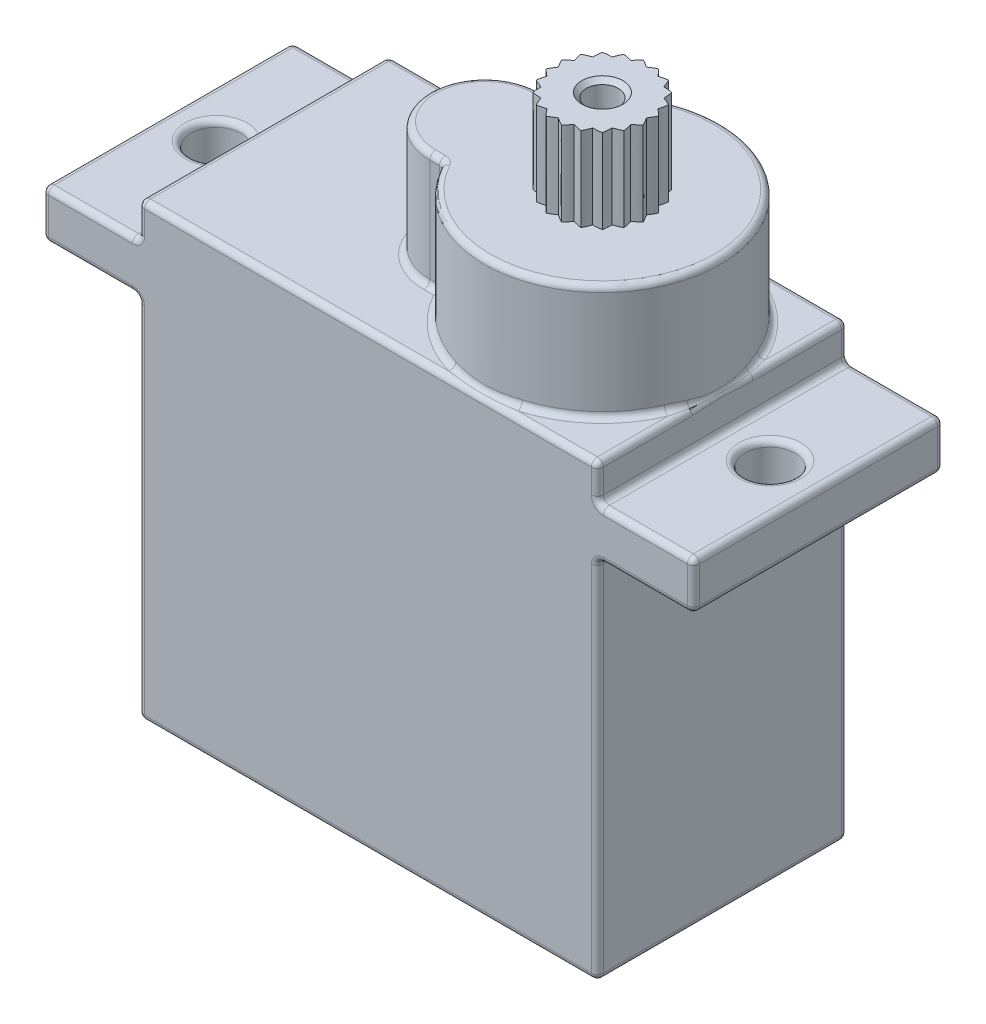
SolidWorks part; units mm, degrees
other "Camera1"
ref_plane "Front" through (0, 0, 0) normal (0, 0, 1) x (1, 0, 0)
ref_plane "Top" through (0, 0, 0) normal (0, 1, 0) x (1, 0, 0)
ref_plane "Right" through (0, 0, 0) normal (1, 0, 0) x (0, 0, -1)
sketch "Sketch1" plane through (0, 0, 0) normal (0, 1, 0) x (1, 0, 0)
  line L1 (11.47, -6.25) -> (-11.47, -6.25)
  line L2 (11.47, -6.25) -> (11.47, 6.25)
  line L3 (11.47, 6.25) -> (-11.47, 6.25)
  line L4 (-11.47, -6.25) -> (-11.47, 6.25)
  line L5 (11.47, -6.25) -> (-11.47, 6.25) construction
  line L6 (11.47, 6.25) -> (-11.47, -6.25) construction
  point P0 (0, 0)
  dimension "D1" = 22.94
  dimension "D2" = 12.5
extrude "Boss-Extrude1" add sketch "Sketch1" along normal blind 22.5
ref_plane "Plane1" through (0, 18.3, 0) normal (0, -1, 0) x (-1, 0, 0)
sketch "Sketch2" plane through (0, 18.3, 0) normal (0, -1, 0) x (-1, 0, 0)
  line L0 (11.47, -6.25) -> (-11.47, -6.25) construction
  line L1 (-11.47, 6.25) -> (-16.27, 6.25)
  line L2 (-11.47, 6.25) -> (-11.47, -6.25)
  line L3 (-11.47, -6.25) -> (-16.27, -6.25)
  line L4 (-16.27, 6.25) -> (-16.27, -6.25)
  line L5 (0, 0) -> (0, -2.4329) construction
  line L6 (11.47, -6.25) -> (16.27, -6.25)
  line L7 (16.27, 6.25) -> (16.27, -6.25)
  line L8 (11.47, 6.25) -> (16.27, 6.25)
  line L9 (11.47, 6.25) -> (11.47, -6.25)
  circle A0 centre (-13.85, 0) radius 1.25
  circle A1 centre (13.85, 0) radius 1.25
  dimension "D2" = 2.5
  dimension "D1" = 4.8
  dimension "D3" = 13.85
extrude "Boss-Extrude2" add sketch "Sketch2" against normal blind 2.4
sketch "Sketch3" plane through (0, 22.5, 0) normal (0, 1, 0) x (1, 0, 0)
  line L0 (11.47, -6.25) -> (11.47, 6.25) construction
  line L1 (11.47, -6.25) -> (11.47, 6.25) construction
  line L2 (-0.41, 2.75) -> (0.2501, 2.75) construction
  line L3 (-0.41, -2.75) -> (0.2501, -2.75) construction
  line L4 (-0.41, 2.75) -> (0.2501, 2.75)
  line L5 (-0.41, -2.75) -> (0.2501, -2.75)
  line L6 (-0.41, 0) -> (5.47, 0) construction
  circle A0 centre (5.47, 0) radius 5.9 construction
  circle A1 centre (-0.41, 0) radius 2.75 construction
  arc A2 (-0.41, -2.75) -> (-0.41, 2.75) centre (-0.41, 0) cw
  arc A3 (0.2501, 2.75) -> (0.2501, -2.75) centre (5.47, 0) cw
  point P4 (11.37, 0)
  point P5 (-3.16, 0)
  dimension "D1" = 6
  dimension "D2" = 11.8
  dimension "D4" = 14.53
  dimension "D5" = 5.5
  dimension "D3" = 0.1
extrude "Boss-Extrude3" add sketch "Sketch3" along normal blind 5.75
sketch "Sketch4" plane through (0, 28.25, 0) normal (0, 1, 0) x (1, 0, 0)
  line L0 (5.47, 0) -> (5.47, 2.2) construction
  line L1 (5.47, 0) -> (6.1498, 2.0923) construction
  line L2 (5.47, 0) -> (5.8142, 2.1729) construction
  line L3 (5.47, 2.2) -> (5.7959, 2.4184) construction
  line L4 (5.7959, 2.4184) -> (5.8533, 2.4198) construction
  line L5 (6.1498, 2.0923) -> (5.9074, 2.4007) construction
  line L6 (5.9074, 2.4007) -> (5.8533, 2.4198) construction
  line L7 (6.1498, 2.0923) -> (6.5272, 2.1993) construction
  line L8 (6.5272, 2.1993) -> (6.5823, 2.183) construction
  line L9 (6.7631, 1.7798) -> (6.6278, 2.148) construction
  line L10 (6.6278, 2.148) -> (6.5823, 2.183) construction
  line L11 (6.7631, 1.7798) -> (7.1551, 1.7649) construction
  line L12 (7.1551, 1.7649) -> (7.2024, 1.7324) construction
  line L13 (7.2498, 1.2931) -> (7.2349, 1.6851) construction
  line L14 (7.2349, 1.6851) -> (7.2024, 1.7324) construction
  line L15 (7.2498, 1.2931) -> (7.618, 1.1578) construction
  line L16 (7.618, 1.1578) -> (7.653, 1.1123) construction
  line L17 (7.5623, 0.6798) -> (7.6693, 1.0572) construction
  line L18 (7.6693, 1.0572) -> (7.653, 1.1123) construction
  line L19 (7.5623, 0.6798) -> (7.8707, 0.4374) construction
  line L20 (7.8707, 0.4374) -> (7.8898, 0.3833) construction
  line L21 (7.67, 0) -> (7.8884, 0.3259) construction
  line L22 (7.8884, 0.3259) -> (7.8898, 0.3833) construction
  line L23 (7.67, 0) -> (7.8884, -0.3259) construction
  line L24 (7.8884, -0.3259) -> (7.8898, -0.3833) construction
  line L25 (7.5623, -0.6798) -> (7.8707, -0.4374) construction
  line L26 (7.8707, -0.4374) -> (7.8898, -0.3833) construction
  line L27 (7.5623, -0.6798) -> (7.6693, -1.0572) construction
  line L28 (7.6693, -1.0572) -> (7.653, -1.1123) construction
  line L29 (7.2498, -1.2931) -> (7.618, -1.1578) construction
  line L30 (7.618, -1.1578) -> (7.653, -1.1123) construction
  line L31 (7.2498, -1.2931) -> (7.2349, -1.6851) construction
  line L32 (7.2349, -1.6851) -> (7.2024, -1.7324) construction
  line L33 (6.7631, -1.7798) -> (7.1551, -1.7649) construction
  line L34 (7.1551, -1.7649) -> (7.2024, -1.7324) construction
  line L35 (6.7631, -1.7798) -> (6.6278, -2.148) construction
  line L36 (6.6278, -2.148) -> (6.5823, -2.183) construction
  line L37 (6.1498, -2.0923) -> (6.5272, -2.1993) construction
  line L38 (6.5272, -2.1993) -> (6.5823, -2.183) construction
  line L39 (6.1498, -2.0923) -> (5.9074, -2.4007) construction
  line L40 (5.9074, -2.4007) -> (5.8533, -2.4198) construction
  line L41 (5.47, -2.2) -> (5.7959, -2.4184) construction
  line L42 (5.7959, -2.4184) -> (5.8533, -2.4198) construction
  line L43 (5.47, -2.2) -> (5.1441, -2.4184) construction
  line L44 (5.1441, -2.4184) -> (5.0867, -2.4198) construction
  line L45 (4.7902, -2.0923) -> (5.0326, -2.4007) construction
  line L46 (5.0326, -2.4007) -> (5.0867, -2.4198) construction
  line L47 (4.7902, -2.0923) -> (4.4128, -2.1993) construction
  line L48 (4.4128, -2.1993) -> (4.3577, -2.183) construction
  line L49 (4.1769, -1.7798) -> (4.3122, -2.148) construction
  line L50 (4.3122, -2.148) -> (4.3577, -2.183) construction
  line L51 (4.1769, -1.7798) -> (3.7849, -1.7649) construction
  line L52 (3.7849, -1.7649) -> (3.7376, -1.7324) construction
  line L53 (3.6902, -1.2931) -> (3.7051, -1.6851) construction
  line L54 (3.7051, -1.6851) -> (3.7376, -1.7324) construction
  line L55 (3.6902, -1.2931) -> (3.322, -1.1578) construction
  line L56 (3.322, -1.1578) -> (3.287, -1.1123) construction
  line L57 (3.3777, -0.6798) -> (3.2707, -1.0572) construction
  line L58 (3.2707, -1.0572) -> (3.287, -1.1123) construction
  line L59 (3.3777, -0.6798) -> (3.0693, -0.4374) construction
  line L60 (3.0693, -0.4374) -> (3.0502, -0.3833) construction
  line L61 (3.27, 0) -> (3.0516, -0.3259) construction
  line L62 (3.0516, -0.3259) -> (3.0502, -0.3833) construction
  line L63 (3.27, 0) -> (3.0516, 0.3259) construction
  line L64 (3.0516, 0.3259) -> (3.0502, 0.3833) construction
  line L65 (3.3777, 0.6798) -> (3.0693, 0.4374) construction
  line L66 (3.0693, 0.4374) -> (3.0502, 0.3833) construction
  line L67 (3.3777, 0.6798) -> (3.2707, 1.0572) construction
  line L68 (3.2707, 1.0572) -> (3.287, 1.1123) construction
  line L69 (3.6902, 1.2931) -> (3.322, 1.1578) construction
  line L70 (3.322, 1.1578) -> (3.287, 1.1123) construction
  line L71 (3.6902, 1.2931) -> (3.7051, 1.6851) construction
  line L72 (3.7051, 1.6851) -> (3.7376, 1.7324) construction
  line L73 (4.1769, 1.7798) -> (3.7849, 1.7649) construction
  line L74 (3.7849, 1.7649) -> (3.7376, 1.7324) construction
  line L75 (4.1769, 1.7798) -> (4.3122, 2.148) construction
  line L76 (4.3122, 2.148) -> (4.3577, 2.183) construction
  line L77 (4.7902, 2.0923) -> (4.4128, 2.1993) construction
  line L78 (4.4128, 2.1993) -> (4.3577, 2.183) construction
  line L79 (4.7902, 2.0923) -> (5.0326, 2.4007) construction
  line L80 (5.0326, 2.4007) -> (5.0867, 2.4198) construction
  line L81 (5.47, 2.2) -> (5.1441, 2.4184) construction
  line L82 (5.1441, 2.4184) -> (5.0867, 2.4198) construction
  circle A0 centre (5.47, 0) radius 2.45 construction
  circle A1 centre (5.47, 0) radius 2.2 construction
  arc A2 (5.47, 2.2) -> (6.1498, 2.0923) centre (5.47, 0) cw construction
  spline S0 degree 2 poles (5.47, 2.2) (5.7959, 2.4184) (5.8533, 2.4198) knots 0 0 0 1 1 1
  spline S1 degree 2 poles (6.1498, 2.0923) (5.9074, 2.4007) (5.8533, 2.4198) knots 0 0 0 1 1 1
  spline S2 degree 2 poles (6.1498, 2.0923) (6.5272, 2.1993) (6.5823, 2.183) knots 0 0 0 1 1 1
  spline S3 degree 2 poles (6.7631, 1.7798) (6.6278, 2.148) (6.5823, 2.183) knots 0 0 0 1 1 1
  spline S4 degree 2 poles (6.7631, 1.7798) (7.1551, 1.7649) (7.2024, 1.7324) knots 0 0 0 1 1 1
  spline S5 degree 2 poles (7.2498, 1.2931) (7.2349, 1.6851) (7.2024, 1.7324) knots 0 0 0 1 1 1
  spline S6 degree 2 poles (7.2498, 1.2931) (7.618, 1.1578) (7.653, 1.1123) knots 0 0 0 1 1 1
  spline S7 degree 2 poles (7.5623, 0.6798) (7.6693, 1.0572) (7.653, 1.1123) knots 0 0 0 1 1 1
  spline S8 degree 2 poles (7.5623, 0.6798) (7.8707, 0.4374) (7.8898, 0.3833) knots 0 0 0 1 1 1
  spline S9 degree 2 poles (7.67, 0) (7.8884, 0.3259) (7.8898, 0.3833) knots 0 0 0 1 1 1
  spline S10 degree 2 poles (7.67, 0) (7.8884, -0.3259) (7.8898, -0.3833) knots 0 0 0 1 1 1
  spline S11 degree 2 poles (7.5623, -0.6798) (7.8707, -0.4374) (7.8898, -0.3833) knots 0 0 0 1 1 1
  spline S12 degree 2 poles (7.5623, -0.6798) (7.6693, -1.0572) (7.653, -1.1123) knots 0 0 0 1 1 1
  spline S13 degree 2 poles (7.2498, -1.2931) (7.618, -1.1578) (7.653, -1.1123) knots 0 0 0 1 1 1
  spline S14 degree 2 poles (7.2498, -1.2931) (7.2349, -1.6851) (7.2024, -1.7324) knots 0 0 0 1 1 1
  spline S15 degree 2 poles (6.7631, -1.7798) (7.1551, -1.7649) (7.2024, -1.7324) knots 0 0 0 1 1 1
  spline S16 degree 2 poles (6.7631, -1.7798) (6.6278, -2.148) (6.5823, -2.183) knots 0 0 0 1 1 1
  spline S17 degree 2 poles (6.1498, -2.0923) (6.5272, -2.1993) (6.5823, -2.183) knots 0 0 0 1 1 1
  spline S18 degree 2 poles (6.1498, -2.0923) (5.9074, -2.4007) (5.8533, -2.4198) knots 0 0 0 1 1 1
  spline S19 degree 2 poles (5.47, -2.2) (5.7959, -2.4184) (5.8533, -2.4198) knots 0 0 0 1 1 1
  spline S20 degree 2 poles (5.47, -2.2) (5.1441, -2.4184) (5.0867, -2.4198) knots 0 0 0 1 1 1
  spline S21 degree 2 poles (4.7902, -2.0923) (5.0326, -2.4007) (5.0867, -2.4198) knots 0 0 0 1 1 1
  spline S22 degree 2 poles (4.7902, -2.0923) (4.4128, -2.1993) (4.3577, -2.183) knots 0 0 0 1 1 1
  spline S23 degree 2 poles (4.1769, -1.7798) (4.3122, -2.148) (4.3577, -2.183) knots 0 0 0 1 1 1
  spline S24 degree 2 poles (4.1769, -1.7798) (3.7849, -1.7649) (3.7376, -1.7324) knots 0 0 0 1 1 1
  spline S25 degree 2 poles (3.6902, -1.2931) (3.7051, -1.6851) (3.7376, -1.7324) knots 0 0 0 1 1 1
  spline S26 degree 2 poles (3.6902, -1.2931) (3.322, -1.1578) (3.287, -1.1123) knots 0 0 0 1 1 1
  spline S27 degree 2 poles (3.3777, -0.6798) (3.2707, -1.0572) (3.287, -1.1123) knots 0 0 0 1 1 1
  spline S28 degree 2 poles (3.3777, -0.6798) (3.0693, -0.4374) (3.0502, -0.3833) knots 0 0 0 1 1 1
  spline S29 degree 2 poles (3.27, 0) (3.0516, -0.3259) (3.0502, -0.3833) knots 0 0 0 1 1 1
  spline S30 degree 2 poles (3.27, 0) (3.0516, 0.3259) (3.0502, 0.3833) knots 0 0 0 1 1 1
  spline S31 degree 2 poles (3.3777, 0.6798) (3.0693, 0.4374) (3.0502, 0.3833) knots 0 0 0 1 1 1
  spline S32 degree 2 poles (3.3777, 0.6798) (3.2707, 1.0572) (3.287, 1.1123) knots 0 0 0 1 1 1
  spline S33 degree 2 poles (3.6902, 1.2931) (3.322, 1.1578) (3.287, 1.1123) knots 0 0 0 1 1 1
  spline S34 degree 2 poles (3.6902, 1.2931) (3.7051, 1.6851) (3.7376, 1.7324) knots 0 0 0 1 1 1
  spline S35 degree 2 poles (4.1769, 1.7798) (3.7849, 1.7649) (3.7376, 1.7324) knots 0 0 0 1 1 1
  spline S36 degree 2 poles (4.1769, 1.7798) (4.3122, 2.148) (4.3577, 2.183) knots 0 0 0 1 1 1
  spline S37 degree 2 poles (4.7902, 2.0923) (4.4128, 2.1993) (4.3577, 2.183) knots 0 0 0 1 1 1
  spline S38 degree 2 poles (4.7902, 2.0923) (5.0326, 2.4007) (5.0867, 2.4198) knots 0 0 0 1 1 1
  spline S39 degree 2 poles (5.47, 2.2) (5.1441, 2.4184) (5.0867, 2.4198) knots 0 0 0 1 1 1
  point P8 (5.47, 2.2)
  point P9 (6.1498, 2.0923)
  point P109 (5.47, 0)
  dimension "D1" = 4.9
  dimension "D2" = 4.4
  dimension "D3" = 18
extrude "Boss-Extrude4" add sketch "Sketch4" along normal blind 4.2 contours S0 S39 S38 S37 S36 S35 S34 S33 S32 S31 S30 S29 S28 S27 S26 S25 S24 S23 S22 S21 S20 S19 S18 S17 S16 S15 S14 S13 S12 S11 S10 S9 S8 S7 S6 S5 S4 S3 S2 S1 region at (5.47, 28.25, 0)
hole_wizard "M2x0.4 Tapped Hole1" positions "Sketch5" profile "Sketch6" tap size "M2x0.4" standard "ANSI Metric"
sketch "Sketch5" plane through (0, 32.45, 0) normal (0, 1, 0) x (1, 0, 0)
  point P0 (5.47, 0)
sketch "Sketch6" plane through (5.47, 32.45, 0) normal (1, 0, 0) x (0, 0, 1)
  line L0 (0, 0) -> (0, 5.6807)
  line L1 (0, 5.6807) -> (0.8, 5.2)
  line L2 (0.8, 5.2) -> (0.8, 0.225)
  line L3 (0.8, 0.225) -> (1.025, 0)
  line L5 (1.025, 0) -> (0, 0)
  line L6 (-0.8, 0.225) -> (-1.025, 0) construction
  line L10 (0, 5.6807) -> (-0.8, 5.2) construction
  line L11 (0, -6.35) -> (0, 107.95) construction
  dimension "Tap Drill Dia." = 1.6
  dimension "Tap Drill Depth" = 5.2
  dimension "Near C'Sink Dia." = 2.05
  dimension "Near C'Sink Angle" = 90
  dimension "Drill Angle" = 118
cosmetic thread "Hole Thread1" parameters "D1"=4, "D2"=2
fillet "Fillet1" radius 0.3 40 edges at (11.47, 22.5, 0) (16.27, 18.3, 0) (13.85, 18.3, -1.25) (16.27, 20.7, 0) (11.47, 20.7, 0) (13.85, 20.7, -1.25) (-16.27, 20.7, 0) (-13.85, 20.7, 1.25) (-16.27, 18.3, 0) (-13.85, 18.3, 1.25) (-11.47, 22.5, 0) (-11.47, 20.7, 0) (-11.47, 18.3, 0) (11.47, 18.3, 0) (11.47, 0, 0) (-11.47, 0, 0) (11.47, 9.15, -6.25) (13.87, 18.3, -6.25) (16.27, 19.5, -6.25) (13.87, 20.7, -6.25) (11.47, 21.6, -6.25) (0, 22.5, -6.25) (-11.47, 21.6, -6.25) (-13.87, 20.7, -6.25) (-16.27, 19.5, -6.25) (-13.87, 18.3, -6.25) (-11.47, 9.15, -6.25) (0, 0, -6.25) (-11.47, 9.15, 6.25) (-13.87, 18.3, 6.25) (-16.27, 19.5, 6.25) (-13.87, 20.7, 6.25) (-11.47, 21.6, 6.25) (0, 22.5, 6.25) (11.47, 21.6, 6.25) (13.87, 20.7, 6.25) (16.27, 19.5, 6.25) (13.87, 18.3, 6.25) (11.47, 9.15, 6.25) (0, 0, 6.25)
fillet "Fillet2" radius 0.3 12 edges at (-0.08, 28.25, -2.75) (-0.08, 28.25, 2.75) (-0.08, 22.5, -2.75) (-0.08, 22.5, 2.75) (-3.16, 28.25, 0) (-3.16, 22.5, 0) (0.2501, 25.375, 2.75) (11.37, 28.25, 0) (0.2501, 25.375, -2.75) (6.1287, 22.5, -5.8631) (11.37, 22.5, 0) (6.1287, 22.5, 5.8631)
ref_axis "Axis1" through (5.47, 27.95, 0) along (0, -1, 0)
